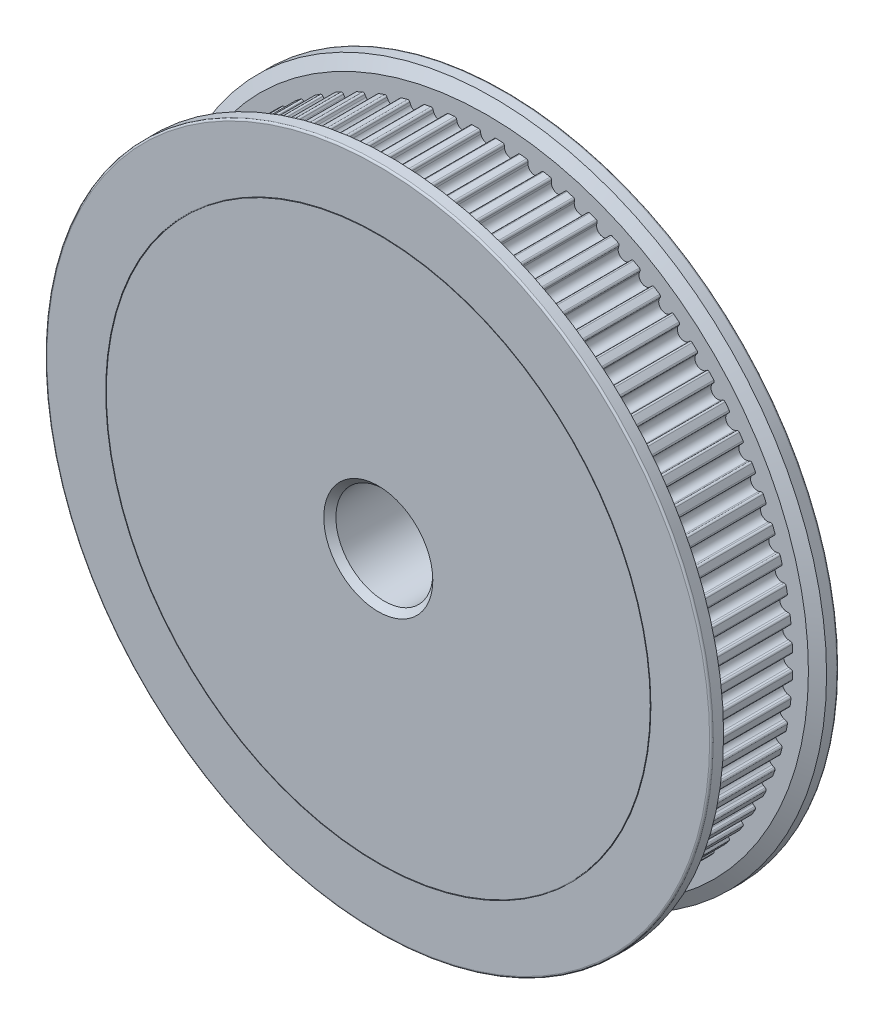
SolidWorks part; units mm, degrees
ref_plane "Front Plane" through (0, 0, 0) normal (0, 0, 1) x (1, 0, 0)
ref_plane "Top Plane" through (0, 0, 0) normal (0, 1, 0) x (1, 0, 0)
ref_plane "Right Plane" through (0, 0, 0) normal (1, 0, 0) x (0, 0, -1)
sketch "Sketch1" plane through (0, 0, 0) normal (0, 0, 1) x (1, 0, 0)
  circle A0 centre (0, 0) radius 15
  dimension "D1" = 30
extrude "Boss-Extrude1" add sketch "Sketch1" along normal blind 6.7
sketch "Sketch2" plane through (0, 0, 6.7) normal (0, 0, 1) x (1, 0, 0)
  circle A0 centre (0, 0) radius 27.5
  dimension "D1" = 55
extrude "Boss-Extrude2" add sketch "Sketch2" along normal blind 1.5 contours A0
sketch "Sketch3" plane through (0, 0, 8.2) normal (0, 0, 1) x (1, 0, 0)
  circle A0 centre (0, 0) radius 25.2
  dimension "D1" = 50.4
extrude "Boss-Extrude3" add sketch "Sketch3" along normal blind 7.5
sketch "Sketch4" plane through (0, 0, 15.7) normal (0, 0, 1) x (1, 0, 0)
  circle A0 centre (0, 0) radius 27.5
extrude "Boss-Extrude4" add sketch "Sketch4" along normal blind 1.5
sketch "Sketch5" plane through (0, 0, 8.2) normal (0, 0, 1) x (1, 0, 0)
  line L0 (0, 0) -> (38.9808, 0) construction
  line L1 (25.1897, 0.7199) -> (25.7855, 0.7199)
  line L2 (25.7855, 0.7199) -> (25.7855, -0.7199)
  line L3 (25.7855, -0.7199) -> (25.1897, -0.7199)
  line L4 (25.1685, -1.2587) -> (25.7625, -1.3054)
  line L5 (25.7625, -1.3054) -> (25.6496, -2.7408)
  line L6 (25.6496, -2.7408) -> (25.0556, -2.694)
  line L7 (24.9922, -3.2295) -> (25.5807, -3.3227)
  line L8 (25.5807, -3.3227) -> (25.3555, -4.7448)
  line L9 (25.3555, -4.7448) -> (24.767, -4.6516)
  line L10 (24.6618, -5.1804) -> (25.2411, -5.3195)
  line L11 (25.2411, -5.3195) -> (24.905, -6.7195)
  line L12 (24.905, -6.7195) -> (24.3257, -6.5804)
  line L13 (24.1793, -7.0994) -> (24.746, -7.2835)
  line L14 (24.746, -7.2835) -> (24.301, -8.6528)
  line L15 (24.301, -8.6528) -> (23.7344, -8.4687)
  line L16 (23.5477, -8.9746) -> (24.0982, -9.2026)
  line L17 (24.0982, -9.2026) -> (23.5472, -10.5328)
  line L18 (23.5472, -10.5328) -> (22.9968, -10.3048)
  line L19 (22.771, -10.7945) -> (23.3019, -11.065)
  line L20 (23.3019, -11.065) -> (22.6483, -12.3478)
  line L21 (22.6483, -12.3478) -> (22.1174, -12.0773)
  line L22 (21.8539, -12.5478) -> (22.3619, -12.8591)
  line L23 (22.3619, -12.8591) -> (21.6096, -14.0867)
  line L24 (21.6096, -14.0867) -> (21.1016, -13.7754)
  line L25 (20.802, -14.2237) -> (21.2841, -14.574)
  line L26 (21.2841, -14.574) -> (20.4378, -15.7388)
  line L27 (20.4378, -15.7388) -> (19.9558, -15.3885)
  line L28 (19.6219, -15.812) -> (20.075, -16.199)
  line L29 (20.075, -16.199) -> (19.1399, -17.2938)
  line L30 (19.1399, -17.2938) -> (18.6869, -16.9068)
  line L31 (18.3209, -17.3028) -> (18.7422, -17.7241)
  line L32 (18.7422, -17.7241) -> (17.7241, -18.7422)
  line L33 (17.7241, -18.7422) -> (17.3028, -18.3209)
  line L34 (16.9068, -18.6869) -> (17.2938, -19.1399)
  line L35 (17.2938, -19.1399) -> (16.199, -20.075)
  line L36 (16.199, -20.075) -> (15.812, -19.6219)
  line L37 (15.3885, -19.9558) -> (15.7388, -20.4378)
  line L38 (15.7388, -20.4378) -> (14.574, -21.2841)
  line L39 (14.574, -21.2841) -> (14.2237, -20.802)
  line L40 (13.7754, -21.1016) -> (14.0867, -21.6096)
  line L41 (14.0867, -21.6096) -> (12.8591, -22.3619)
  line L42 (12.8591, -22.3619) -> (12.5478, -21.8539)
  line L43 (12.0773, -22.1174) -> (12.3478, -22.6483)
  line L44 (12.3478, -22.6483) -> (11.065, -23.3019)
  line L45 (11.065, -23.3019) -> (10.7945, -22.771)
  line L46 (10.3048, -22.9968) -> (10.5328, -23.5472)
  line L47 (10.5328, -23.5472) -> (9.2026, -24.0982)
  line L48 (9.2026, -24.0982) -> (8.9746, -23.5477)
  line L49 (8.4687, -23.7344) -> (8.6528, -24.301)
  line L50 (8.6528, -24.301) -> (7.2835, -24.746)
  line L51 (7.2835, -24.746) -> (7.0994, -24.1793)
  line L52 (6.5804, -24.3257) -> (6.7195, -24.905)
  line L53 (6.7195, -24.905) -> (5.3195, -25.2411)
  line L54 (5.3195, -25.2411) -> (5.1804, -24.6618)
  line L55 (4.6516, -24.767) -> (4.7448, -25.3555)
  line L56 (4.7448, -25.3555) -> (3.3227, -25.5807)
  line L57 (3.3227, -25.5807) -> (3.2295, -24.9922)
  line L58 (2.694, -25.0556) -> (2.7408, -25.6496)
  line L59 (2.7408, -25.6496) -> (1.3054, -25.7625)
  line L60 (1.3054, -25.7625) -> (1.2587, -25.1685)
  line L61 (0.7199, -25.1897) -> (0.7199, -25.7855)
  line L62 (0.7199, -25.7855) -> (-0.7199, -25.7855)
  line L63 (-0.7199, -25.7855) -> (-0.7199, -25.1897)
  line L64 (-1.2587, -25.1685) -> (-1.3054, -25.7625)
  line L65 (-1.3054, -25.7625) -> (-2.7408, -25.6496)
  line L66 (-2.7408, -25.6496) -> (-2.694, -25.0556)
  line L67 (-3.2295, -24.9922) -> (-3.3227, -25.5807)
  line L68 (-3.3227, -25.5807) -> (-4.7448, -25.3555)
  line L69 (-4.7448, -25.3555) -> (-4.6516, -24.767)
  line L70 (-5.1804, -24.6618) -> (-5.3195, -25.2411)
  line L71 (-5.3195, -25.2411) -> (-6.7195, -24.905)
  line L72 (-6.7195, -24.905) -> (-6.5804, -24.3257)
  line L73 (-7.0994, -24.1793) -> (-7.2835, -24.746)
  line L74 (-7.2835, -24.746) -> (-8.6528, -24.301)
  line L75 (-8.6528, -24.301) -> (-8.4687, -23.7344)
  line L76 (-8.9746, -23.5477) -> (-9.2026, -24.0982)
  line L77 (-9.2026, -24.0982) -> (-10.5328, -23.5472)
  line L78 (-10.5328, -23.5472) -> (-10.3048, -22.9968)
  line L79 (-10.7945, -22.771) -> (-11.065, -23.3019)
  line L80 (-11.065, -23.3019) -> (-12.3478, -22.6483)
  line L81 (-12.3478, -22.6483) -> (-12.0773, -22.1174)
  line L82 (-12.5478, -21.8539) -> (-12.8591, -22.3619)
  line L83 (-12.8591, -22.3619) -> (-14.0867, -21.6096)
  line L84 (-14.0867, -21.6096) -> (-13.7754, -21.1016)
  line L85 (-14.2237, -20.802) -> (-14.574, -21.2841)
  line L86 (-14.574, -21.2841) -> (-15.7388, -20.4378)
  line L87 (-15.7388, -20.4378) -> (-15.3885, -19.9558)
  line L88 (-15.812, -19.6219) -> (-16.199, -20.075)
  line L89 (-16.199, -20.075) -> (-17.2938, -19.1399)
  line L90 (-17.2938, -19.1399) -> (-16.9068, -18.6869)
  line L91 (-17.3028, -18.3209) -> (-17.7241, -18.7422)
  line L92 (-17.7241, -18.7422) -> (-18.7422, -17.7241)
  line L93 (-18.7422, -17.7241) -> (-18.3209, -17.3028)
  line L94 (-18.6869, -16.9068) -> (-19.1399, -17.2938)
  line L95 (-19.1399, -17.2938) -> (-20.075, -16.199)
  line L96 (-20.075, -16.199) -> (-19.6219, -15.812)
  line L97 (-19.9558, -15.3885) -> (-20.4378, -15.7388)
  line L98 (-20.4378, -15.7388) -> (-21.2841, -14.574)
  line L99 (-21.2841, -14.574) -> (-20.802, -14.2237)
  line L100 (-21.1016, -13.7754) -> (-21.6096, -14.0867)
  line L101 (-21.6096, -14.0867) -> (-22.3619, -12.8591)
  line L102 (-22.3619, -12.8591) -> (-21.8539, -12.5478)
  line L103 (-22.1174, -12.0773) -> (-22.6483, -12.3478)
  line L104 (-22.6483, -12.3478) -> (-23.3019, -11.065)
  line L105 (-23.3019, -11.065) -> (-22.771, -10.7945)
  line L106 (-22.9968, -10.3048) -> (-23.5472, -10.5328)
  line L107 (-23.5472, -10.5328) -> (-24.0982, -9.2026)
  line L108 (-24.0982, -9.2026) -> (-23.5477, -8.9746)
  line L109 (-23.7344, -8.4687) -> (-24.301, -8.6528)
  line L110 (-24.301, -8.6528) -> (-24.746, -7.2835)
  line L111 (-24.746, -7.2835) -> (-24.1793, -7.0994)
  line L112 (-24.3257, -6.5804) -> (-24.905, -6.7195)
  line L113 (-24.905, -6.7195) -> (-25.2411, -5.3195)
  line L114 (-25.2411, -5.3195) -> (-24.6618, -5.1804)
  line L115 (-24.767, -4.6516) -> (-25.3555, -4.7448)
  line L116 (-25.3555, -4.7448) -> (-25.5807, -3.3227)
  line L117 (-25.5807, -3.3227) -> (-24.9922, -3.2295)
  line L118 (-25.0556, -2.694) -> (-25.6496, -2.7408)
  line L119 (-25.6496, -2.7408) -> (-25.7625, -1.3054)
  line L120 (-25.7625, -1.3054) -> (-25.1685, -1.2587)
  line L121 (-25.1897, -0.7199) -> (-25.7855, -0.7199)
  line L122 (-25.7855, -0.7199) -> (-25.7855, 0.7199)
  line L123 (-25.7855, 0.7199) -> (-25.1897, 0.7199)
  line L124 (-25.1685, 1.2587) -> (-25.7625, 1.3054)
  line L125 (-25.7625, 1.3054) -> (-25.6496, 2.7408)
  line L126 (-25.6496, 2.7408) -> (-25.0556, 2.694)
  line L127 (-24.9922, 3.2295) -> (-25.5807, 3.3227)
  line L128 (-25.5807, 3.3227) -> (-25.3555, 4.7448)
  line L129 (-25.3555, 4.7448) -> (-24.767, 4.6516)
  line L130 (-24.6618, 5.1804) -> (-25.2411, 5.3195)
  line L131 (-25.2411, 5.3195) -> (-24.905, 6.7195)
  line L132 (-24.905, 6.7195) -> (-24.3257, 6.5804)
  line L133 (-24.1793, 7.0994) -> (-24.746, 7.2835)
  line L134 (-24.746, 7.2835) -> (-24.301, 8.6528)
  line L135 (-24.301, 8.6528) -> (-23.7344, 8.4687)
  line L136 (-23.5477, 8.9746) -> (-24.0982, 9.2026)
  line L137 (-24.0982, 9.2026) -> (-23.5472, 10.5328)
  line L138 (-23.5472, 10.5328) -> (-22.9968, 10.3048)
  line L139 (-22.771, 10.7945) -> (-23.3019, 11.065)
  line L140 (-23.3019, 11.065) -> (-22.6483, 12.3478)
  line L141 (-22.6483, 12.3478) -> (-22.1174, 12.0773)
  line L142 (-21.8539, 12.5478) -> (-22.3619, 12.8591)
  line L143 (-22.3619, 12.8591) -> (-21.6096, 14.0867)
  line L144 (-21.6096, 14.0867) -> (-21.1016, 13.7754)
  line L145 (-20.802, 14.2237) -> (-21.2841, 14.574)
  line L146 (-21.2841, 14.574) -> (-20.4378, 15.7388)
  line L147 (-20.4378, 15.7388) -> (-19.9558, 15.3885)
  line L148 (-19.6219, 15.812) -> (-20.075, 16.199)
  line L149 (-20.075, 16.199) -> (-19.1399, 17.2938)
  line L150 (-19.1399, 17.2938) -> (-18.6869, 16.9068)
  line L151 (-18.3209, 17.3028) -> (-18.7422, 17.7241)
  line L152 (-18.7422, 17.7241) -> (-17.7241, 18.7422)
  line L153 (-17.7241, 18.7422) -> (-17.3028, 18.3209)
  line L154 (-16.9068, 18.6869) -> (-17.2938, 19.1399)
  line L155 (-17.2938, 19.1399) -> (-16.199, 20.075)
  line L156 (-16.199, 20.075) -> (-15.812, 19.6219)
  line L157 (-15.3885, 19.9558) -> (-15.7388, 20.4378)
  line L158 (-15.7388, 20.4378) -> (-14.574, 21.2841)
  line L159 (-14.574, 21.2841) -> (-14.2237, 20.802)
  line L160 (-13.7754, 21.1016) -> (-14.0867, 21.6096)
  line L161 (-14.0867, 21.6096) -> (-12.8591, 22.3619)
  line L162 (-12.8591, 22.3619) -> (-12.5478, 21.8539)
  line L163 (-12.0773, 22.1174) -> (-12.3478, 22.6483)
  line L164 (-12.3478, 22.6483) -> (-11.065, 23.3019)
  line L165 (-11.065, 23.3019) -> (-10.7945, 22.771)
  line L166 (-10.3048, 22.9968) -> (-10.5328, 23.5472)
  line L167 (-10.5328, 23.5472) -> (-9.2026, 24.0982)
  line L168 (-9.2026, 24.0982) -> (-8.9746, 23.5477)
  line L169 (-8.4687, 23.7344) -> (-8.6528, 24.301)
  line L170 (-8.6528, 24.301) -> (-7.2835, 24.746)
  line L171 (-7.2835, 24.746) -> (-7.0994, 24.1793)
  line L172 (-6.5804, 24.3257) -> (-6.7195, 24.905)
  line L173 (-6.7195, 24.905) -> (-5.3195, 25.2411)
  line L174 (-5.3195, 25.2411) -> (-5.1804, 24.6618)
  line L175 (-4.6516, 24.767) -> (-4.7448, 25.3555)
  line L176 (-4.7448, 25.3555) -> (-3.3227, 25.5807)
  line L177 (-3.3227, 25.5807) -> (-3.2295, 24.9922)
  line L178 (-2.694, 25.0556) -> (-2.7408, 25.6496)
  line L179 (-2.7408, 25.6496) -> (-1.3054, 25.7625)
  line L180 (-1.3054, 25.7625) -> (-1.2587, 25.1685)
  line L181 (-0.7199, 25.1897) -> (-0.7199, 25.7855)
  line L182 (-0.7199, 25.7855) -> (0.7199, 25.7855)
  line L183 (0.7199, 25.7855) -> (0.7199, 25.1897)
  line L184 (1.2587, 25.1685) -> (1.3054, 25.7625)
  line L185 (1.3054, 25.7625) -> (2.7408, 25.6496)
  line L186 (2.7408, 25.6496) -> (2.694, 25.0556)
  line L187 (3.2295, 24.9922) -> (3.3227, 25.5807)
  line L188 (3.3227, 25.5807) -> (4.7448, 25.3555)
  line L189 (4.7448, 25.3555) -> (4.6516, 24.767)
  line L190 (5.1804, 24.6618) -> (5.3195, 25.2411)
  line L191 (5.3195, 25.2411) -> (6.7195, 24.905)
  line L192 (6.7195, 24.905) -> (6.5804, 24.3257)
  line L193 (7.0994, 24.1793) -> (7.2835, 24.746)
  line L194 (7.2835, 24.746) -> (8.6528, 24.301)
  line L195 (8.6528, 24.301) -> (8.4687, 23.7344)
  line L196 (8.9746, 23.5477) -> (9.2026, 24.0982)
  line L197 (9.2026, 24.0982) -> (10.5328, 23.5472)
  line L198 (10.5328, 23.5472) -> (10.3048, 22.9968)
  line L199 (10.7945, 22.771) -> (11.065, 23.3019)
  line L200 (11.065, 23.3019) -> (12.3478, 22.6483)
  line L201 (12.3478, 22.6483) -> (12.0773, 22.1174)
  line L202 (12.5478, 21.8539) -> (12.8591, 22.3619)
  line L203 (12.8591, 22.3619) -> (14.0867, 21.6096)
  line L204 (14.0867, 21.6096) -> (13.7754, 21.1016)
  line L205 (14.2237, 20.802) -> (14.574, 21.2841)
  line L206 (14.574, 21.2841) -> (15.7388, 20.4378)
  line L207 (15.7388, 20.4378) -> (15.3885, 19.9558)
  line L208 (15.812, 19.6219) -> (16.199, 20.075)
  line L209 (16.199, 20.075) -> (17.2938, 19.1399)
  line L210 (17.2938, 19.1399) -> (16.9068, 18.6869)
  line L211 (17.3028, 18.3209) -> (17.7241, 18.7422)
  line L212 (17.7241, 18.7422) -> (18.7422, 17.7241)
  line L213 (18.7422, 17.7241) -> (18.3209, 17.3028)
  line L214 (18.6869, 16.9068) -> (19.1399, 17.2938)
  line L215 (19.1399, 17.2938) -> (20.075, 16.199)
  line L216 (20.075, 16.199) -> (19.6219, 15.812)
  line L217 (19.9558, 15.3885) -> (20.4378, 15.7388)
  line L218 (20.4378, 15.7388) -> (21.2841, 14.574)
  line L219 (21.2841, 14.574) -> (20.802, 14.2237)
  line L220 (21.1016, 13.7754) -> (21.6096, 14.0867)
  line L221 (21.6096, 14.0867) -> (22.3619, 12.8591)
  line L222 (22.3619, 12.8591) -> (21.8539, 12.5478)
  line L223 (22.1174, 12.0773) -> (22.6483, 12.3478)
  line L224 (22.6483, 12.3478) -> (23.3019, 11.065)
  line L225 (23.3019, 11.065) -> (22.771, 10.7945)
  line L226 (22.9968, 10.3048) -> (23.5472, 10.5328)
  line L227 (23.5472, 10.5328) -> (24.0982, 9.2026)
  line L228 (24.0982, 9.2026) -> (23.5477, 8.9746)
  line L229 (23.7344, 8.4687) -> (24.301, 8.6528)
  line L230 (24.301, 8.6528) -> (24.746, 7.2835)
  line L231 (24.746, 7.2835) -> (24.1793, 7.0994)
  line L232 (24.3257, 6.5804) -> (24.905, 6.7195)
  line L233 (24.905, 6.7195) -> (25.2411, 5.3195)
  line L234 (25.2411, 5.3195) -> (24.6618, 5.1804)
  line L235 (24.767, 4.6516) -> (25.3555, 4.7448)
  line L236 (25.3555, 4.7448) -> (25.5807, 3.3227)
  line L237 (25.5807, 3.3227) -> (24.9922, 3.2295)
  line L238 (25.0556, 2.694) -> (25.6496, 2.7408)
  line L239 (25.6496, 2.7408) -> (25.7625, 1.3054)
  line L240 (25.7625, 1.3054) -> (25.1685, 1.2587)
  circle A0 centre (0, 0) radius 25.45 construction
  circle A1 centre (0, 0) radius 25.2 construction
  arc A2 (24.8691, 0.5381) -> (24.8691, -0.5381) centre (25.005, 0) ccw
  arc A4 (24.8346, -1.4148) -> (24.7502, -2.4876) centre (24.9279, -1.9619) ccw
  arc A5 (25.0159, -1.4012) -> (25.1685, -1.2587) centre (25.0187, -1.2512) ccw
  arc A6 (25.0487, 0.5659) -> (25.1897, 0.7199) centre (25.0398, 0.7156) ccw
  arc A7 (25.0487, -0.5659) -> (25.1897, -0.7199) centre (25.0398, -0.7156) cw
  arc A8 (25.0487, 0.5659) -> (24.8691, 0.5381) centre (25.106, -0.4) ccw
  arc A9 (25.0487, -0.5659) -> (24.8691, -0.5381) centre (25.106, 0.4) cw
  arc A10 (24.9271, -2.5294) -> (25.0556, -2.694) centre (24.9064, -2.678) cw
  arc A11 (25.0159, -1.4012) -> (24.8346, -1.4148) centre (24.9973, -2.3686) ccw
  arc A12 (24.9271, -2.5294) -> (24.7502, -2.4876) centre (25.06, -1.571) cw
  circle A13 centre (0, 0) radius 25.45 construction
  circle A14 centre (0, 0) radius 25.2 construction
  arc A15 (24.6471, -3.3589) -> (24.4787, -4.4219) centre (24.6971, -3.9116) ccw
  arc A16 (24.8288, -3.3596) -> (24.9922, -3.2295) centre (24.8434, -3.2103) ccw
  arc A17 (24.6518, -4.4774) -> (24.767, -4.6516) centre (24.6196, -4.6239) cw
  arc A18 (24.8288, -3.3596) -> (24.6471, -3.3589) centre (24.7344, -4.3225) ccw
  arc A19 (24.6518, -4.4774) -> (24.4787, -4.4219) centre (24.8595, -3.5324) cw
  circle A20 centre (0, 0) radius 25.45 construction
  circle A21 centre (0, 0) radius 25.2 construction
  arc A22 (24.3076, -5.2823) -> (24.0563, -6.3288) centre (24.3141, -5.8373) ccw
  arc A23 (24.4887, -5.2973) -> (24.6618, -5.1804) centre (24.515, -5.1496) ccw
  arc A24 (24.2245, -6.3977) -> (24.3257, -6.5804) centre (24.1809, -6.5412) cw
  arc A25 (24.4887, -5.2973) -> (24.3076, -5.2823) centre (24.319, -6.2498) ccw
  arc A26 (24.2245, -6.3977) -> (24.0563, -6.3288) centre (24.5057, -5.4719) cw
  circle A27 centre (0, 0) radius 25.45 construction
  circle A28 centre (0, 0) radius 25.2 construction
  arc A29 (23.8182, -7.1732) -> (23.4856, -8.1967) centre (23.7812, -7.727) ccw
  arc A30 (23.9976, -7.2023) -> (24.1793, -7.0994) centre (24.0354, -7.0571) ccw
  arc A31 (23.6478, -8.2786) -> (23.7344, -8.4687) centre (23.5931, -8.4183) cw
  arc A32 (23.9976, -7.2023) -> (23.8182, -7.1732) centre (23.7537, -8.1386) ccw
  arc A33 (23.6478, -8.2786) -> (23.4856, -8.1967) centre (24.0009, -7.3778) cw
  circle A34 centre (0, 0) radius 25.45 construction
  circle A35 centre (0, 0) radius 25.2 construction
  arc A36 (23.182, -9.0198) -> (22.7701, -10.0141) centre (23.1016, -9.569) ccw
  arc A37 (23.3585, -9.0629) -> (23.5477, -8.9746) centre (23.4076, -8.9212) ccw
  arc A38 (22.9254, -10.1085) -> (22.9968, -10.3048) centre (22.8599, -10.2434) cw
  arc A39 (23.3585, -9.0629) -> (23.182, -9.0198) centre (23.0419, -9.9772) ccw
  arc A40 (22.9254, -10.1085) -> (22.7701, -10.0141) centre (23.348, -9.2381) cw
  circle A41 centre (0, 0) radius 25.45 construction
  circle A42 centre (0, 0) radius 25.2 construction
  arc A43 (22.4028, -10.8109) -> (21.9142, -11.7698) centre (22.2796, -11.352) ccw
  arc A44 (22.5754, -10.8677) -> (22.771, -10.7945) centre (22.6355, -10.7302) ccw
  arc A45 (22.0616, -11.876) -> (22.1174, -12.0773) centre (21.9857, -12.0054) cw
  arc A46 (22.5754, -10.8677) -> (22.4028, -10.8109) centre (22.188, -11.7543) ccw
  arc A47 (22.0616, -11.876) -> (21.9142, -11.7698) centre (22.5512, -11.0415) cw
  circle A48 centre (0, 0) radius 25.45 construction
  circle A49 centre (0, 0) radius 25.2 construction
  arc A50 (21.4855, -12.5353) -> (20.9232, -13.4529) centre (21.3203, -13.0651) ccw
  arc A51 (21.6532, -12.6054) -> (21.8539, -12.5478) centre (21.7238, -12.4731) ccw
  arc A52 (21.0618, -13.5704) -> (21.1016, -13.7754) centre (20.976, -13.6934) cw
  arc A53 (21.6532, -12.6054) -> (21.4855, -12.5353) centre (21.1974, -13.4589) ccw
  arc A54 (21.0618, -13.5704) -> (20.9232, -13.4529) centre (21.6154, -12.7768) cw
  circle A55 centre (0, 0) radius 25.45 construction
  circle A56 centre (0, 0) radius 25.2 construction
  arc A57 (20.4358, -14.1823) -> (19.8032, -15.053) centre (20.2295, -14.6976) ccw
  arc A58 (20.5974, -14.2654) -> (20.802, -14.2237) centre (20.6782, -14.1391) ccw
  arc A59 (19.9322, -15.181) -> (19.9558, -15.3885) centre (19.837, -15.2969) cw
  arc A60 (20.5974, -14.2654) -> (20.4358, -14.1823) centre (20.0761, -15.0806) ccw
  arc A61 (19.9322, -15.181) -> (19.8032, -15.053) centre (20.5463, -14.4334) cw
  circle A62 centre (0, 0) radius 25.45 construction
  circle A63 centre (0, 0) radius 25.2 construction
  arc A64 (19.2601, -15.742) -> (18.5611, -16.5603) centre (19.014, -16.2394) ccw
  arc A65 (19.4147, -15.8375) -> (19.6219, -15.812) centre (19.5051, -15.7179) ccw
  arc A66 (18.6797, -16.6981) -> (18.6869, -16.9068) centre (18.5757, -16.8062) cw
  arc A67 (19.4147, -15.8375) -> (19.2601, -15.742) centre (18.831, -16.6092) ccw
  arc A68 (18.6797, -16.6981) -> (18.5611, -16.5603) centre (19.3506, -16.0009) cw
  circle A69 centre (0, 0) radius 25.45 construction
  circle A70 centre (0, 0) radius 25.2 construction
  arc A71 (17.9656, -17.2046) -> (17.2046, -17.9656) centre (17.6812, -17.6812) ccw
  arc A72 (18.1122, -17.312) -> (18.3209, -17.3028) centre (18.2118, -17.1998) ccw
  arc A73 (17.312, -18.1122) -> (17.3028, -18.3209) centre (17.1998, -18.2118) cw
  arc A74 (18.1122, -17.312) -> (17.9656, -17.2046) centre (17.4698, -18.0355) ccw
  arc A75 (17.312, -18.1122) -> (17.2046, -17.9656) centre (18.0355, -17.4698) cw
  circle A76 centre (0, 0) radius 25.45 construction
  circle A77 centre (0, 0) radius 25.2 construction
  arc A78 (16.5603, -18.5611) -> (15.742, -19.2601) centre (16.2394, -19.014) ccw
  arc A79 (16.6981, -18.6797) -> (16.9068, -18.6869) centre (16.8062, -18.5757) ccw
  arc A80 (15.8375, -19.4147) -> (15.812, -19.6219) centre (15.7179, -19.5051) cw
  arc A81 (16.6981, -18.6797) -> (16.5603, -18.5611) centre (16.0009, -19.3506) ccw
  arc A82 (15.8375, -19.4147) -> (15.742, -19.2601) centre (16.6092, -18.831) cw
  circle A83 centre (0, 0) radius 25.45 construction
  circle A84 centre (0, 0) radius 25.2 construction
  arc A85 (15.053, -19.8032) -> (14.1823, -20.4358) centre (14.6976, -20.2295) ccw
  arc A86 (15.181, -19.9322) -> (15.3885, -19.9558) centre (15.2969, -19.837) ccw
  arc A87 (14.2654, -20.5974) -> (14.2237, -20.802) centre (14.1391, -20.6782) cw
  arc A88 (15.181, -19.9322) -> (15.053, -19.8032) centre (14.4334, -20.5463) ccw
  arc A89 (14.2654, -20.5974) -> (14.1823, -20.4358) centre (15.0806, -20.0761) cw
  circle A90 centre (0, 0) radius 25.45 construction
  circle A91 centre (0, 0) radius 25.2 construction
  arc A92 (13.4529, -20.9232) -> (12.5353, -21.4855) centre (13.0651, -21.3203) ccw
  arc A93 (13.5704, -21.0618) -> (13.7754, -21.1016) centre (13.6934, -20.976) ccw
  arc A94 (12.6054, -21.6532) -> (12.5478, -21.8539) centre (12.4731, -21.7238) cw
  arc A95 (13.5704, -21.0618) -> (13.4529, -20.9232) centre (12.7768, -21.6154) ccw
  arc A96 (12.6054, -21.6532) -> (12.5353, -21.4855) centre (13.4589, -21.1974) cw
  circle A97 centre (0, 0) radius 25.45 construction
  circle A98 centre (0, 0) radius 25.2 construction
  arc A99 (11.7698, -21.9142) -> (10.8109, -22.4028) centre (11.352, -22.2796) ccw
  arc A100 (11.876, -22.0616) -> (12.0773, -22.1174) centre (12.0054, -21.9857) ccw
  arc A101 (10.8677, -22.5754) -> (10.7945, -22.771) centre (10.7302, -22.6355) cw
  arc A102 (11.876, -22.0616) -> (11.7698, -21.9142) centre (11.0415, -22.5512) ccw
  arc A103 (10.8677, -22.5754) -> (10.8109, -22.4028) centre (11.7543, -22.188) cw
  circle A104 centre (0, 0) radius 25.45 construction
  circle A105 centre (0, 0) radius 25.2 construction
  arc A106 (10.0141, -22.7701) -> (9.0198, -23.182) centre (9.569, -23.1016) ccw
  arc A107 (10.1085, -22.9254) -> (10.3048, -22.9968) centre (10.2434, -22.8599) ccw
  arc A108 (9.0629, -23.3585) -> (8.9746, -23.5477) centre (8.9212, -23.4076) cw
  arc A109 (10.1085, -22.9254) -> (10.0141, -22.7701) centre (9.2381, -23.348) ccw
  arc A110 (9.0629, -23.3585) -> (9.0198, -23.182) centre (9.9772, -23.0419) cw
  circle A111 centre (0, 0) radius 25.45 construction
  circle A112 centre (0, 0) radius 25.2 construction
  arc A113 (8.1967, -23.4856) -> (7.1732, -23.8182) centre (7.727, -23.7812) ccw
  arc A114 (8.2786, -23.6478) -> (8.4687, -23.7344) centre (8.4183, -23.5931) ccw
  arc A115 (7.2023, -23.9976) -> (7.0994, -24.1793) centre (7.0571, -24.0354) cw
  arc A116 (8.2786, -23.6478) -> (8.1967, -23.4856) centre (7.3778, -24.0009) ccw
  arc A117 (7.2023, -23.9976) -> (7.1732, -23.8182) centre (8.1386, -23.7537) cw
  circle A118 centre (0, 0) radius 25.45 construction
  circle A119 centre (0, 0) radius 25.2 construction
  arc A120 (6.3288, -24.0563) -> (5.2823, -24.3076) centre (5.8373, -24.3141) ccw
  arc A121 (6.3977, -24.2245) -> (6.5804, -24.3257) centre (6.5412, -24.1809) ccw
  arc A122 (5.2973, -24.4887) -> (5.1804, -24.6618) centre (5.1496, -24.515) cw
  arc A123 (6.3977, -24.2245) -> (6.3288, -24.0563) centre (5.4719, -24.5057) ccw
  arc A124 (5.2973, -24.4887) -> (5.2823, -24.3076) centre (6.2498, -24.319) cw
  circle A125 centre (0, 0) radius 25.45 construction
  circle A126 centre (0, 0) radius 25.2 construction
  arc A127 (4.4219, -24.4787) -> (3.3589, -24.6471) centre (3.9116, -24.6971) ccw
  arc A128 (4.4774, -24.6518) -> (4.6516, -24.767) centre (4.6239, -24.6196) ccw
  arc A129 (3.3596, -24.8288) -> (3.2295, -24.9922) centre (3.2103, -24.8434) cw
  arc A130 (4.4774, -24.6518) -> (4.4219, -24.4787) centre (3.5324, -24.8595) ccw
  arc A131 (3.3596, -24.8288) -> (3.3589, -24.6471) centre (4.3225, -24.7344) cw
  circle A132 centre (0, 0) radius 25.45 construction
  circle A133 centre (0, 0) radius 25.2 construction
  arc A134 (2.4876, -24.7502) -> (1.4148, -24.8346) centre (1.9619, -24.9279) ccw
  arc A135 (2.5294, -24.9271) -> (2.694, -25.0556) centre (2.678, -24.9064) ccw
  arc A136 (1.4012, -25.0159) -> (1.2587, -25.1685) centre (1.2512, -25.0187) cw
  arc A137 (2.5294, -24.9271) -> (2.4876, -24.7502) centre (1.571, -25.06) ccw
  arc A138 (1.4012, -25.0159) -> (1.4148, -24.8346) centre (2.3686, -24.9973) cw
  circle A139 centre (0, 0) radius 25.45 construction
  circle A140 centre (0, 0) radius 25.2 construction
  arc A141 (0.5381, -24.8691) -> (-0.5381, -24.8691) centre (0, -25.005) ccw
  arc A142 (0.5659, -25.0487) -> (0.7199, -25.1897) centre (0.7156, -25.0398) ccw
  arc A143 (-0.5659, -25.0487) -> (-0.7199, -25.1897) centre (-0.7156, -25.0398) cw
  arc A144 (0.5659, -25.0487) -> (0.5381, -24.8691) centre (-0.4, -25.106) ccw
  arc A145 (-0.5659, -25.0487) -> (-0.5381, -24.8691) centre (0.4, -25.106) cw
  circle A146 centre (0, 0) radius 25.45 construction
  circle A147 centre (0, 0) radius 25.2 construction
  arc A148 (-1.4148, -24.8346) -> (-2.4876, -24.7502) centre (-1.9619, -24.9279) ccw
  arc A149 (-1.4012, -25.0159) -> (-1.2587, -25.1685) centre (-1.2512, -25.0187) ccw
  arc A150 (-2.5294, -24.9271) -> (-2.694, -25.0556) centre (-2.678, -24.9064) cw
  arc A151 (-1.4012, -25.0159) -> (-1.4148, -24.8346) centre (-2.3686, -24.9973) ccw
  arc A152 (-2.5294, -24.9271) -> (-2.4876, -24.7502) centre (-1.571, -25.06) cw
  circle A153 centre (0, 0) radius 25.45 construction
  circle A154 centre (0, 0) radius 25.2 construction
  arc A155 (-3.3589, -24.6471) -> (-4.4219, -24.4787) centre (-3.9116, -24.6971) ccw
  arc A156 (-3.3596, -24.8288) -> (-3.2295, -24.9922) centre (-3.2103, -24.8434) ccw
  arc A157 (-4.4774, -24.6518) -> (-4.6516, -24.767) centre (-4.6239, -24.6196) cw
  arc A158 (-3.3596, -24.8288) -> (-3.3589, -24.6471) centre (-4.3225, -24.7344) ccw
  arc A159 (-4.4774, -24.6518) -> (-4.4219, -24.4787) centre (-3.5324, -24.8595) cw
  circle A160 centre (0, 0) radius 25.45 construction
  circle A161 centre (0, 0) radius 25.2 construction
  arc A162 (-5.2823, -24.3076) -> (-6.3288, -24.0563) centre (-5.8373, -24.3141) ccw
  arc A163 (-5.2973, -24.4887) -> (-5.1804, -24.6618) centre (-5.1496, -24.515) ccw
  arc A164 (-6.3977, -24.2245) -> (-6.5804, -24.3257) centre (-6.5412, -24.1809) cw
  arc A165 (-5.2973, -24.4887) -> (-5.2823, -24.3076) centre (-6.2498, -24.319) ccw
  arc A166 (-6.3977, -24.2245) -> (-6.3288, -24.0563) centre (-5.4719, -24.5057) cw
  circle A167 centre (0, 0) radius 25.45 construction
  circle A168 centre (0, 0) radius 25.2 construction
  arc A169 (-7.1732, -23.8182) -> (-8.1967, -23.4856) centre (-7.727, -23.7812) ccw
  arc A170 (-7.2023, -23.9976) -> (-7.0994, -24.1793) centre (-7.0571, -24.0354) ccw
  arc A171 (-8.2786, -23.6478) -> (-8.4687, -23.7344) centre (-8.4183, -23.5931) cw
  arc A172 (-7.2023, -23.9976) -> (-7.1732, -23.8182) centre (-8.1386, -23.7537) ccw
  arc A173 (-8.2786, -23.6478) -> (-8.1967, -23.4856) centre (-7.3778, -24.0009) cw
  circle A174 centre (0, 0) radius 25.45 construction
  circle A175 centre (0, 0) radius 25.2 construction
  arc A176 (-9.0198, -23.182) -> (-10.0141, -22.7701) centre (-9.569, -23.1016) ccw
  arc A177 (-9.0629, -23.3585) -> (-8.9746, -23.5477) centre (-8.9212, -23.4076) ccw
  arc A178 (-10.1085, -22.9254) -> (-10.3048, -22.9968) centre (-10.2434, -22.8599) cw
  arc A179 (-9.0629, -23.3585) -> (-9.0198, -23.182) centre (-9.9772, -23.0419) ccw
  arc A180 (-10.1085, -22.9254) -> (-10.0141, -22.7701) centre (-9.2381, -23.348) cw
  circle A181 centre (0, 0) radius 25.45 construction
  circle A182 centre (0, 0) radius 25.2 construction
  arc A183 (-10.8109, -22.4028) -> (-11.7698, -21.9142) centre (-11.352, -22.2796) ccw
  arc A184 (-10.8677, -22.5754) -> (-10.7945, -22.771) centre (-10.7302, -22.6355) ccw
  arc A185 (-11.876, -22.0616) -> (-12.0773, -22.1174) centre (-12.0054, -21.9857) cw
  arc A186 (-10.8677, -22.5754) -> (-10.8109, -22.4028) centre (-11.7543, -22.188) ccw
  arc A187 (-11.876, -22.0616) -> (-11.7698, -21.9142) centre (-11.0415, -22.5512) cw
  circle A188 centre (0, 0) radius 25.45 construction
  circle A189 centre (0, 0) radius 25.2 construction
  arc A190 (-12.5353, -21.4855) -> (-13.4529, -20.9232) centre (-13.0651, -21.3203) ccw
  arc A191 (-12.6054, -21.6532) -> (-12.5478, -21.8539) centre (-12.4731, -21.7238) ccw
  arc A192 (-13.5704, -21.0618) -> (-13.7754, -21.1016) centre (-13.6934, -20.976) cw
  arc A193 (-12.6054, -21.6532) -> (-12.5353, -21.4855) centre (-13.4589, -21.1974) ccw
  arc A194 (-13.5704, -21.0618) -> (-13.4529, -20.9232) centre (-12.7768, -21.6154) cw
  circle A195 centre (0, 0) radius 25.45 construction
  circle A196 centre (0, 0) radius 25.2 construction
  arc A197 (-14.1823, -20.4358) -> (-15.053, -19.8032) centre (-14.6976, -20.2295) ccw
  arc A198 (-14.2654, -20.5974) -> (-14.2237, -20.802) centre (-14.1391, -20.6782) ccw
  arc A199 (-15.181, -19.9322) -> (-15.3885, -19.9558) centre (-15.2969, -19.837) cw
  arc A200 (-14.2654, -20.5974) -> (-14.1823, -20.4358) centre (-15.0806, -20.0761) ccw
  arc A201 (-15.181, -19.9322) -> (-15.053, -19.8032) centre (-14.4334, -20.5463) cw
  circle A202 centre (0, 0) radius 25.45 construction
  circle A203 centre (0, 0) radius 25.2 construction
  arc A204 (-15.742, -19.2601) -> (-16.5603, -18.5611) centre (-16.2394, -19.014) ccw
  arc A205 (-15.8375, -19.4147) -> (-15.812, -19.6219) centre (-15.7179, -19.5051) ccw
  arc A206 (-16.6981, -18.6797) -> (-16.9068, -18.6869) centre (-16.8062, -18.5757) cw
  arc A207 (-15.8375, -19.4147) -> (-15.742, -19.2601) centre (-16.6092, -18.831) ccw
  arc A208 (-16.6981, -18.6797) -> (-16.5603, -18.5611) centre (-16.0009, -19.3506) cw
  circle A209 centre (0, 0) radius 25.45 construction
  circle A210 centre (0, 0) radius 25.2 construction
  arc A211 (-17.2046, -17.9656) -> (-17.9656, -17.2046) centre (-17.6812, -17.6812) ccw
  arc A212 (-17.312, -18.1122) -> (-17.3028, -18.3209) centre (-17.1998, -18.2118) ccw
  arc A213 (-18.1122, -17.312) -> (-18.3209, -17.3028) centre (-18.2118, -17.1998) cw
  arc A214 (-17.312, -18.1122) -> (-17.2046, -17.9656) centre (-18.0355, -17.4698) ccw
  arc A215 (-18.1122, -17.312) -> (-17.9656, -17.2046) centre (-17.4698, -18.0355) cw
  circle A216 centre (0, 0) radius 25.45 construction
  circle A217 centre (0, 0) radius 25.2 construction
  arc A218 (-18.5611, -16.5603) -> (-19.2601, -15.742) centre (-19.014, -16.2394) ccw
  arc A219 (-18.6797, -16.6981) -> (-18.6869, -16.9068) centre (-18.5757, -16.8062) ccw
  arc A220 (-19.4147, -15.8375) -> (-19.6219, -15.812) centre (-19.5051, -15.7179) cw
  arc A221 (-18.6797, -16.6981) -> (-18.5611, -16.5603) centre (-19.3506, -16.0009) ccw
  arc A222 (-19.4147, -15.8375) -> (-19.2601, -15.742) centre (-18.831, -16.6092) cw
  circle A223 centre (0, 0) radius 25.45 construction
  circle A224 centre (0, 0) radius 25.2 construction
  arc A225 (-19.8032, -15.053) -> (-20.4358, -14.1823) centre (-20.2295, -14.6976) ccw
  arc A226 (-19.9322, -15.181) -> (-19.9558, -15.3885) centre (-19.837, -15.2969) ccw
  arc A227 (-20.5974, -14.2654) -> (-20.802, -14.2237) centre (-20.6782, -14.1391) cw
  arc A228 (-19.9322, -15.181) -> (-19.8032, -15.053) centre (-20.5463, -14.4334) ccw
  arc A229 (-20.5974, -14.2654) -> (-20.4358, -14.1823) centre (-20.0761, -15.0806) cw
  circle A230 centre (0, 0) radius 25.45 construction
  circle A231 centre (0, 0) radius 25.2 construction
  arc A232 (-20.9232, -13.4529) -> (-21.4855, -12.5353) centre (-21.3203, -13.0651) ccw
  arc A233 (-21.0618, -13.5704) -> (-21.1016, -13.7754) centre (-20.976, -13.6934) ccw
  arc A234 (-21.6532, -12.6054) -> (-21.8539, -12.5478) centre (-21.7238, -12.4731) cw
  arc A235 (-21.0618, -13.5704) -> (-20.9232, -13.4529) centre (-21.6154, -12.7768) ccw
  arc A236 (-21.6532, -12.6054) -> (-21.4855, -12.5353) centre (-21.1974, -13.4589) cw
  circle A237 centre (0, 0) radius 25.45 construction
  circle A238 centre (0, 0) radius 25.2 construction
  arc A239 (-21.9142, -11.7698) -> (-22.4028, -10.8109) centre (-22.2796, -11.352) ccw
  arc A240 (-22.0616, -11.876) -> (-22.1174, -12.0773) centre (-21.9857, -12.0054) ccw
  arc A241 (-22.5754, -10.8677) -> (-22.771, -10.7945) centre (-22.6355, -10.7302) cw
  arc A242 (-22.0616, -11.876) -> (-21.9142, -11.7698) centre (-22.5512, -11.0415) ccw
  arc A243 (-22.5754, -10.8677) -> (-22.4028, -10.8109) centre (-22.188, -11.7543) cw
  circle A244 centre (0, 0) radius 25.45 construction
  circle A245 centre (0, 0) radius 25.2 construction
  arc A246 (-22.7701, -10.0141) -> (-23.182, -9.0198) centre (-23.1016, -9.569) ccw
  arc A247 (-22.9254, -10.1085) -> (-22.9968, -10.3048) centre (-22.8599, -10.2434) ccw
  arc A248 (-23.3585, -9.0629) -> (-23.5477, -8.9746) centre (-23.4076, -8.9212) cw
  arc A249 (-22.9254, -10.1085) -> (-22.7701, -10.0141) centre (-23.348, -9.2381) ccw
  arc A250 (-23.3585, -9.0629) -> (-23.182, -9.0198) centre (-23.0419, -9.9772) cw
  circle A251 centre (0, 0) radius 25.45 construction
  circle A252 centre (0, 0) radius 25.2 construction
  arc A253 (-23.4856, -8.1967) -> (-23.8182, -7.1732) centre (-23.7812, -7.727) ccw
  arc A254 (-23.6478, -8.2786) -> (-23.7344, -8.4687) centre (-23.5931, -8.4183) ccw
  arc A255 (-23.9976, -7.2023) -> (-24.1793, -7.0994) centre (-24.0354, -7.0571) cw
  arc A256 (-23.6478, -8.2786) -> (-23.4856, -8.1967) centre (-24.0009, -7.3778) ccw
  arc A257 (-23.9976, -7.2023) -> (-23.8182, -7.1732) centre (-23.7537, -8.1386) cw
  circle A258 centre (0, 0) radius 25.45 construction
  circle A259 centre (0, 0) radius 25.2 construction
  arc A260 (-24.0563, -6.3288) -> (-24.3076, -5.2823) centre (-24.3141, -5.8373) ccw
  arc A261 (-24.2245, -6.3977) -> (-24.3257, -6.5804) centre (-24.1809, -6.5412) ccw
  arc A262 (-24.4887, -5.2973) -> (-24.6618, -5.1804) centre (-24.515, -5.1496) cw
  arc A263 (-24.2245, -6.3977) -> (-24.0563, -6.3288) centre (-24.5057, -5.4719) ccw
  arc A264 (-24.4887, -5.2973) -> (-24.3076, -5.2823) centre (-24.319, -6.2498) cw
  circle A265 centre (0, 0) radius 25.45 construction
  circle A266 centre (0, 0) radius 25.2 construction
  arc A267 (-24.4787, -4.4219) -> (-24.6471, -3.3589) centre (-24.6971, -3.9116) ccw
  arc A268 (-24.6518, -4.4774) -> (-24.767, -4.6516) centre (-24.6196, -4.6239) ccw
  arc A269 (-24.8288, -3.3596) -> (-24.9922, -3.2295) centre (-24.8434, -3.2103) cw
  arc A270 (-24.6518, -4.4774) -> (-24.4787, -4.4219) centre (-24.8595, -3.5324) ccw
  arc A271 (-24.8288, -3.3596) -> (-24.6471, -3.3589) centre (-24.7344, -4.3225) cw
  circle A272 centre (0, 0) radius 25.45 construction
  circle A273 centre (0, 0) radius 25.2 construction
  arc A274 (-24.7502, -2.4876) -> (-24.8346, -1.4148) centre (-24.9279, -1.9619) ccw
  arc A275 (-24.9271, -2.5294) -> (-25.0556, -2.694) centre (-24.9064, -2.678) ccw
  arc A276 (-25.0159, -1.4012) -> (-25.1685, -1.2587) centre (-25.0187, -1.2512) cw
  arc A277 (-24.9271, -2.5294) -> (-24.7502, -2.4876) centre (-25.06, -1.571) ccw
  arc A278 (-25.0159, -1.4012) -> (-24.8346, -1.4148) centre (-24.9973, -2.3686) cw
  circle A279 centre (0, 0) radius 25.45 construction
  circle A280 centre (0, 0) radius 25.2 construction
  arc A281 (-24.8691, -0.5381) -> (-24.8691, 0.5381) centre (-25.005, 0) ccw
  arc A282 (-25.0487, -0.5659) -> (-25.1897, -0.7199) centre (-25.0398, -0.7156) ccw
  arc A283 (-25.0487, 0.5659) -> (-25.1897, 0.7199) centre (-25.0398, 0.7156) cw
  arc A284 (-25.0487, -0.5659) -> (-24.8691, -0.5381) centre (-25.106, 0.4) ccw
  arc A285 (-25.0487, 0.5659) -> (-24.8691, 0.5381) centre (-25.106, -0.4) cw
  circle A286 centre (0, 0) radius 25.45 construction
  circle A287 centre (0, 0) radius 25.2 construction
  arc A288 (-24.8346, 1.4148) -> (-24.7502, 2.4876) centre (-24.9279, 1.9619) ccw
  arc A289 (-25.0159, 1.4012) -> (-25.1685, 1.2587) centre (-25.0187, 1.2512) ccw
  arc A290 (-24.9271, 2.5294) -> (-25.0556, 2.694) centre (-24.9064, 2.678) cw
  arc A291 (-25.0159, 1.4012) -> (-24.8346, 1.4148) centre (-24.9973, 2.3686) ccw
  arc A292 (-24.9271, 2.5294) -> (-24.7502, 2.4876) centre (-25.06, 1.571) cw
  circle A293 centre (0, 0) radius 25.45 construction
  circle A294 centre (0, 0) radius 25.2 construction
  arc A295 (-24.6471, 3.3589) -> (-24.4787, 4.4219) centre (-24.6971, 3.9116) ccw
  arc A296 (-24.8288, 3.3596) -> (-24.9922, 3.2295) centre (-24.8434, 3.2103) ccw
  arc A297 (-24.6518, 4.4774) -> (-24.767, 4.6516) centre (-24.6196, 4.6239) cw
  arc A298 (-24.8288, 3.3596) -> (-24.6471, 3.3589) centre (-24.7344, 4.3225) ccw
  arc A299 (-24.6518, 4.4774) -> (-24.4787, 4.4219) centre (-24.8595, 3.5324) cw
  circle A300 centre (0, 0) radius 25.45 construction
  circle A301 centre (0, 0) radius 25.2 construction
  arc A302 (-24.3076, 5.2823) -> (-24.0563, 6.3288) centre (-24.3141, 5.8373) ccw
  arc A303 (-24.4887, 5.2973) -> (-24.6618, 5.1804) centre (-24.515, 5.1496) ccw
  arc A304 (-24.2245, 6.3977) -> (-24.3257, 6.5804) centre (-24.1809, 6.5412) cw
  arc A305 (-24.4887, 5.2973) -> (-24.3076, 5.2823) centre (-24.319, 6.2498) ccw
  arc A306 (-24.2245, 6.3977) -> (-24.0563, 6.3288) centre (-24.5057, 5.4719) cw
  circle A307 centre (0, 0) radius 25.45 construction
  circle A308 centre (0, 0) radius 25.2 construction
  arc A309 (-23.8182, 7.1732) -> (-23.4856, 8.1967) centre (-23.7812, 7.727) ccw
  arc A310 (-23.9976, 7.2023) -> (-24.1793, 7.0994) centre (-24.0354, 7.0571) ccw
  arc A311 (-23.6478, 8.2786) -> (-23.7344, 8.4687) centre (-23.5931, 8.4183) cw
  arc A312 (-23.9976, 7.2023) -> (-23.8182, 7.1732) centre (-23.7537, 8.1386) ccw
  arc A313 (-23.6478, 8.2786) -> (-23.4856, 8.1967) centre (-24.0009, 7.3778) cw
  circle A314 centre (0, 0) radius 25.45 construction
  circle A315 centre (0, 0) radius 25.2 construction
  arc A316 (-23.182, 9.0198) -> (-22.7701, 10.0141) centre (-23.1016, 9.569) ccw
  arc A317 (-23.3585, 9.0629) -> (-23.5477, 8.9746) centre (-23.4076, 8.9212) ccw
  arc A318 (-22.9254, 10.1085) -> (-22.9968, 10.3048) centre (-22.8599, 10.2434) cw
  arc A319 (-23.3585, 9.0629) -> (-23.182, 9.0198) centre (-23.0419, 9.9772) ccw
  arc A320 (-22.9254, 10.1085) -> (-22.7701, 10.0141) centre (-23.348, 9.2381) cw
  circle A321 centre (0, 0) radius 25.45 construction
  circle A322 centre (0, 0) radius 25.2 construction
  arc A323 (-22.4028, 10.8109) -> (-21.9142, 11.7698) centre (-22.2796, 11.352) ccw
  arc A324 (-22.5754, 10.8677) -> (-22.771, 10.7945) centre (-22.6355, 10.7302) ccw
  arc A325 (-22.0616, 11.876) -> (-22.1174, 12.0773) centre (-21.9857, 12.0054) cw
  arc A326 (-22.5754, 10.8677) -> (-22.4028, 10.8109) centre (-22.188, 11.7543) ccw
  arc A327 (-22.0616, 11.876) -> (-21.9142, 11.7698) centre (-22.5512, 11.0415) cw
  circle A328 centre (0, 0) radius 25.45 construction
  circle A329 centre (0, 0) radius 25.2 construction
  arc A330 (-21.4855, 12.5353) -> (-20.9232, 13.4529) centre (-21.3203, 13.0651) ccw
  arc A331 (-21.6532, 12.6054) -> (-21.8539, 12.5478) centre (-21.7238, 12.4731) ccw
  arc A332 (-21.0618, 13.5704) -> (-21.1016, 13.7754) centre (-20.976, 13.6934) cw
  arc A333 (-21.6532, 12.6054) -> (-21.4855, 12.5353) centre (-21.1974, 13.4589) ccw
  arc A334 (-21.0618, 13.5704) -> (-20.9232, 13.4529) centre (-21.6154, 12.7768) cw
  circle A335 centre (0, 0) radius 25.45 construction
  circle A336 centre (0, 0) radius 25.2 construction
  arc A337 (-20.4358, 14.1823) -> (-19.8032, 15.053) centre (-20.2295, 14.6976) ccw
  arc A338 (-20.5974, 14.2654) -> (-20.802, 14.2237) centre (-20.6782, 14.1391) ccw
  arc A339 (-19.9322, 15.181) -> (-19.9558, 15.3885) centre (-19.837, 15.2969) cw
  arc A340 (-20.5974, 14.2654) -> (-20.4358, 14.1823) centre (-20.0761, 15.0806) ccw
  arc A341 (-19.9322, 15.181) -> (-19.8032, 15.053) centre (-20.5463, 14.4334) cw
  circle A342 centre (0, 0) radius 25.45 construction
  circle A343 centre (0, 0) radius 25.2 construction
  arc A344 (-19.2601, 15.742) -> (-18.5611, 16.5603) centre (-19.014, 16.2394) ccw
  arc A345 (-19.4147, 15.8375) -> (-19.6219, 15.812) centre (-19.5051, 15.7179) ccw
  arc A346 (-18.6797, 16.6981) -> (-18.6869, 16.9068) centre (-18.5757, 16.8062) cw
  arc A347 (-19.4147, 15.8375) -> (-19.2601, 15.742) centre (-18.831, 16.6092) ccw
  arc A348 (-18.6797, 16.6981) -> (-18.5611, 16.5603) centre (-19.3506, 16.0009) cw
  circle A349 centre (0, 0) radius 25.45 construction
  circle A350 centre (0, 0) radius 25.2 construction
  arc A351 (-17.9656, 17.2046) -> (-17.2046, 17.9656) centre (-17.6812, 17.6812) ccw
  arc A352 (-18.1122, 17.312) -> (-18.3209, 17.3028) centre (-18.2118, 17.1998) ccw
  arc A353 (-17.312, 18.1122) -> (-17.3028, 18.3209) centre (-17.1998, 18.2118) cw
  arc A354 (-18.1122, 17.312) -> (-17.9656, 17.2046) centre (-17.4698, 18.0355) ccw
  arc A355 (-17.312, 18.1122) -> (-17.2046, 17.9656) centre (-18.0355, 17.4698) cw
  circle A356 centre (0, 0) radius 25.45 construction
  circle A357 centre (0, 0) radius 25.2 construction
  arc A358 (-16.5603, 18.5611) -> (-15.742, 19.2601) centre (-16.2394, 19.014) ccw
  arc A359 (-16.6981, 18.6797) -> (-16.9068, 18.6869) centre (-16.8062, 18.5757) ccw
  arc A360 (-15.8375, 19.4147) -> (-15.812, 19.6219) centre (-15.7179, 19.5051) cw
  arc A361 (-16.6981, 18.6797) -> (-16.5603, 18.5611) centre (-16.0009, 19.3506) ccw
  arc A362 (-15.8375, 19.4147) -> (-15.742, 19.2601) centre (-16.6092, 18.831) cw
  circle A363 centre (0, 0) radius 25.45 construction
  circle A364 centre (0, 0) radius 25.2 construction
  arc A365 (-15.053, 19.8032) -> (-14.1823, 20.4358) centre (-14.6976, 20.2295) ccw
  arc A366 (-15.181, 19.9322) -> (-15.3885, 19.9558) centre (-15.2969, 19.837) ccw
  arc A367 (-14.2654, 20.5974) -> (-14.2237, 20.802) centre (-14.1391, 20.6782) cw
  arc A368 (-15.181, 19.9322) -> (-15.053, 19.8032) centre (-14.4334, 20.5463) ccw
  arc A369 (-14.2654, 20.5974) -> (-14.1823, 20.4358) centre (-15.0806, 20.0761) cw
  circle A370 centre (0, 0) radius 25.45 construction
  circle A371 centre (0, 0) radius 25.2 construction
  arc A372 (-13.4529, 20.9232) -> (-12.5353, 21.4855) centre (-13.0651, 21.3203) ccw
  arc A373 (-13.5704, 21.0618) -> (-13.7754, 21.1016) centre (-13.6934, 20.976) ccw
  arc A374 (-12.6054, 21.6532) -> (-12.5478, 21.8539) centre (-12.4731, 21.7238) cw
  arc A375 (-13.5704, 21.0618) -> (-13.4529, 20.9232) centre (-12.7768, 21.6154) ccw
  arc A376 (-12.6054, 21.6532) -> (-12.5353, 21.4855) centre (-13.4589, 21.1974) cw
  circle A377 centre (0, 0) radius 25.45 construction
  circle A378 centre (0, 0) radius 25.2 construction
  arc A379 (-11.7698, 21.9142) -> (-10.8109, 22.4028) centre (-11.352, 22.2796) ccw
  arc A380 (-11.876, 22.0616) -> (-12.0773, 22.1174) centre (-12.0054, 21.9857) ccw
  arc A381 (-10.8677, 22.5754) -> (-10.7945, 22.771) centre (-10.7302, 22.6355) cw
  arc A382 (-11.876, 22.0616) -> (-11.7698, 21.9142) centre (-11.0415, 22.5512) ccw
  arc A383 (-10.8677, 22.5754) -> (-10.8109, 22.4028) centre (-11.7543, 22.188) cw
  circle A384 centre (0, 0) radius 25.45 construction
  circle A385 centre (0, 0) radius 25.2 construction
  arc A386 (-10.0141, 22.7701) -> (-9.0198, 23.182) centre (-9.569, 23.1016) ccw
  arc A387 (-10.1085, 22.9254) -> (-10.3048, 22.9968) centre (-10.2434, 22.8599) ccw
  arc A388 (-9.0629, 23.3585) -> (-8.9746, 23.5477) centre (-8.9212, 23.4076) cw
  arc A389 (-10.1085, 22.9254) -> (-10.0141, 22.7701) centre (-9.2381, 23.348) ccw
  arc A390 (-9.0629, 23.3585) -> (-9.0198, 23.182) centre (-9.9772, 23.0419) cw
  circle A391 centre (0, 0) radius 25.45 construction
  circle A392 centre (0, 0) radius 25.2 construction
  arc A393 (-8.1967, 23.4856) -> (-7.1732, 23.8182) centre (-7.727, 23.7812) ccw
  arc A394 (-8.2786, 23.6478) -> (-8.4687, 23.7344) centre (-8.4183, 23.5931) ccw
  arc A395 (-7.2023, 23.9976) -> (-7.0994, 24.1793) centre (-7.0571, 24.0354) cw
  arc A396 (-8.2786, 23.6478) -> (-8.1967, 23.4856) centre (-7.3778, 24.0009) ccw
  arc A397 (-7.2023, 23.9976) -> (-7.1732, 23.8182) centre (-8.1386, 23.7537) cw
  circle A398 centre (0, 0) radius 25.45 construction
  circle A399 centre (0, 0) radius 25.2 construction
  arc A400 (-6.3288, 24.0563) -> (-5.2823, 24.3076) centre (-5.8373, 24.3141) ccw
  arc A401 (-6.3977, 24.2245) -> (-6.5804, 24.3257) centre (-6.5412, 24.1809) ccw
  arc A402 (-5.2973, 24.4887) -> (-5.1804, 24.6618) centre (-5.1496, 24.515) cw
  arc A403 (-6.3977, 24.2245) -> (-6.3288, 24.0563) centre (-5.4719, 24.5057) ccw
  arc A404 (-5.2973, 24.4887) -> (-5.2823, 24.3076) centre (-6.2498, 24.319) cw
  circle A405 centre (0, 0) radius 25.45 construction
  circle A406 centre (0, 0) radius 25.2 construction
  arc A407 (-4.4219, 24.4787) -> (-3.3589, 24.6471) centre (-3.9116, 24.6971) ccw
  arc A408 (-4.4774, 24.6518) -> (-4.6516, 24.767) centre (-4.6239, 24.6196) ccw
  arc A409 (-3.3596, 24.8288) -> (-3.2295, 24.9922) centre (-3.2103, 24.8434) cw
  arc A410 (-4.4774, 24.6518) -> (-4.4219, 24.4787) centre (-3.5324, 24.8595) ccw
  arc A411 (-3.3596, 24.8288) -> (-3.3589, 24.6471) centre (-4.3225, 24.7344) cw
  circle A412 centre (0, 0) radius 25.45 construction
  circle A413 centre (0, 0) radius 25.2 construction
  arc A414 (-2.4876, 24.7502) -> (-1.4148, 24.8346) centre (-1.9619, 24.9279) ccw
  arc A415 (-2.5294, 24.9271) -> (-2.694, 25.0556) centre (-2.678, 24.9064) ccw
  arc A416 (-1.4012, 25.0159) -> (-1.2587, 25.1685) centre (-1.2512, 25.0187) cw
  arc A417 (-2.5294, 24.9271) -> (-2.4876, 24.7502) centre (-1.571, 25.06) ccw
  arc A418 (-1.4012, 25.0159) -> (-1.4148, 24.8346) centre (-2.3686, 24.9973) cw
  circle A419 centre (0, 0) radius 25.45 construction
  circle A420 centre (0, 0) radius 25.2 construction
  arc A421 (-0.5381, 24.8691) -> (0.5381, 24.8691) centre (0, 25.005) ccw
  arc A422 (-0.5659, 25.0487) -> (-0.7199, 25.1897) centre (-0.7156, 25.0398) ccw
  arc A423 (0.5659, 25.0487) -> (0.7199, 25.1897) centre (0.7156, 25.0398) cw
  arc A424 (-0.5659, 25.0487) -> (-0.5381, 24.8691) centre (0.4, 25.106) ccw
  arc A425 (0.5659, 25.0487) -> (0.5381, 24.8691) centre (-0.4, 25.106) cw
  circle A426 centre (0, 0) radius 25.45 construction
  circle A427 centre (0, 0) radius 25.2 construction
  arc A428 (1.4148, 24.8346) -> (2.4876, 24.7502) centre (1.9619, 24.9279) ccw
  arc A429 (1.4012, 25.0159) -> (1.2587, 25.1685) centre (1.2512, 25.0187) ccw
  arc A430 (2.5294, 24.9271) -> (2.694, 25.0556) centre (2.678, 24.9064) cw
  arc A431 (1.4012, 25.0159) -> (1.4148, 24.8346) centre (2.3686, 24.9973) ccw
  arc A432 (2.5294, 24.9271) -> (2.4876, 24.7502) centre (1.571, 25.06) cw
  circle A433 centre (0, 0) radius 25.45 construction
  circle A434 centre (0, 0) radius 25.2 construction
  arc A435 (3.3589, 24.6471) -> (4.4219, 24.4787) centre (3.9116, 24.6971) ccw
  arc A436 (3.3596, 24.8288) -> (3.2295, 24.9922) centre (3.2103, 24.8434) ccw
  arc A437 (4.4774, 24.6518) -> (4.6516, 24.767) centre (4.6239, 24.6196) cw
  arc A438 (3.3596, 24.8288) -> (3.3589, 24.6471) centre (4.3225, 24.7344) ccw
  arc A439 (4.4774, 24.6518) -> (4.4219, 24.4787) centre (3.5324, 24.8595) cw
  circle A440 centre (0, 0) radius 25.45 construction
  circle A441 centre (0, 0) radius 25.2 construction
  arc A442 (5.2823, 24.3076) -> (6.3288, 24.0563) centre (5.8373, 24.3141) ccw
  arc A443 (5.2973, 24.4887) -> (5.1804, 24.6618) centre (5.1496, 24.515) ccw
  arc A444 (6.3977, 24.2245) -> (6.5804, 24.3257) centre (6.5412, 24.1809) cw
  arc A445 (5.2973, 24.4887) -> (5.2823, 24.3076) centre (6.2498, 24.319) ccw
  arc A446 (6.3977, 24.2245) -> (6.3288, 24.0563) centre (5.4719, 24.5057) cw
  circle A447 centre (0, 0) radius 25.45 construction
  circle A448 centre (0, 0) radius 25.2 construction
  arc A449 (7.1732, 23.8182) -> (8.1967, 23.4856) centre (7.727, 23.7812) ccw
  arc A450 (7.2023, 23.9976) -> (7.0994, 24.1793) centre (7.0571, 24.0354) ccw
  arc A451 (8.2786, 23.6478) -> (8.4687, 23.7344) centre (8.4183, 23.5931) cw
  arc A452 (7.2023, 23.9976) -> (7.1732, 23.8182) centre (8.1386, 23.7537) ccw
  arc A453 (8.2786, 23.6478) -> (8.1967, 23.4856) centre (7.3778, 24.0009) cw
  circle A454 centre (0, 0) radius 25.45 construction
  circle A455 centre (0, 0) radius 25.2 construction
  arc A456 (9.0198, 23.182) -> (10.0141, 22.7701) centre (9.569, 23.1016) ccw
  arc A457 (9.0629, 23.3585) -> (8.9746, 23.5477) centre (8.9212, 23.4076) ccw
  arc A458 (10.1085, 22.9254) -> (10.3048, 22.9968) centre (10.2434, 22.8599) cw
  arc A459 (9.0629, 23.3585) -> (9.0198, 23.182) centre (9.9772, 23.0419) ccw
  arc A460 (10.1085, 22.9254) -> (10.0141, 22.7701) centre (9.2381, 23.348) cw
  circle A461 centre (0, 0) radius 25.45 construction
  circle A462 centre (0, 0) radius 25.2 construction
  arc A463 (10.8109, 22.4028) -> (11.7698, 21.9142) centre (11.352, 22.2796) ccw
  arc A464 (10.8677, 22.5754) -> (10.7945, 22.771) centre (10.7302, 22.6355) ccw
  arc A465 (11.876, 22.0616) -> (12.0773, 22.1174) centre (12.0054, 21.9857) cw
  arc A466 (10.8677, 22.5754) -> (10.8109, 22.4028) centre (11.7543, 22.188) ccw
  arc A467 (11.876, 22.0616) -> (11.7698, 21.9142) centre (11.0415, 22.5512) cw
  circle A468 centre (0, 0) radius 25.45 construction
  circle A469 centre (0, 0) radius 25.2 construction
  arc A470 (12.5353, 21.4855) -> (13.4529, 20.9232) centre (13.0651, 21.3203) ccw
  arc A471 (12.6054, 21.6532) -> (12.5478, 21.8539) centre (12.4731, 21.7238) ccw
  arc A472 (13.5704, 21.0618) -> (13.7754, 21.1016) centre (13.6934, 20.976) cw
  arc A473 (12.6054, 21.6532) -> (12.5353, 21.4855) centre (13.4589, 21.1974) ccw
  arc A474 (13.5704, 21.0618) -> (13.4529, 20.9232) centre (12.7768, 21.6154) cw
  circle A475 centre (0, 0) radius 25.45 construction
  circle A476 centre (0, 0) radius 25.2 construction
  arc A477 (14.1823, 20.4358) -> (15.053, 19.8032) centre (14.6976, 20.2295) ccw
  arc A478 (14.2654, 20.5974) -> (14.2237, 20.802) centre (14.1391, 20.6782) ccw
  arc A479 (15.181, 19.9322) -> (15.3885, 19.9558) centre (15.2969, 19.837) cw
  arc A480 (14.2654, 20.5974) -> (14.1823, 20.4358) centre (15.0806, 20.0761) ccw
  arc A481 (15.181, 19.9322) -> (15.053, 19.8032) centre (14.4334, 20.5463) cw
  circle A482 centre (0, 0) radius 25.45 construction
  circle A483 centre (0, 0) radius 25.2 construction
  arc A484 (15.742, 19.2601) -> (16.5603, 18.5611) centre (16.2394, 19.014) ccw
  arc A485 (15.8375, 19.4147) -> (15.812, 19.6219) centre (15.7179, 19.5051) ccw
  arc A486 (16.6981, 18.6797) -> (16.9068, 18.6869) centre (16.8062, 18.5757) cw
  arc A487 (15.8375, 19.4147) -> (15.742, 19.2601) centre (16.6092, 18.831) ccw
  arc A488 (16.6981, 18.6797) -> (16.5603, 18.5611) centre (16.0009, 19.3506) cw
  circle A489 centre (0, 0) radius 25.45 construction
  circle A490 centre (0, 0) radius 25.2 construction
  arc A491 (17.2046, 17.9656) -> (17.9656, 17.2046) centre (17.6812, 17.6812) ccw
  arc A492 (17.312, 18.1122) -> (17.3028, 18.3209) centre (17.1998, 18.2118) ccw
  arc A493 (18.1122, 17.312) -> (18.3209, 17.3028) centre (18.2118, 17.1998) cw
  arc A494 (17.312, 18.1122) -> (17.2046, 17.9656) centre (18.0355, 17.4698) ccw
  arc A495 (18.1122, 17.312) -> (17.9656, 17.2046) centre (17.4698, 18.0355) cw
  circle A496 centre (0, 0) radius 25.45 construction
  circle A497 centre (0, 0) radius 25.2 construction
  arc A498 (18.5611, 16.5603) -> (19.2601, 15.742) centre (19.014, 16.2394) ccw
  arc A499 (18.6797, 16.6981) -> (18.6869, 16.9068) centre (18.5757, 16.8062) ccw
  arc A500 (19.4147, 15.8375) -> (19.6219, 15.812) centre (19.5051, 15.7179) cw
  arc A501 (18.6797, 16.6981) -> (18.5611, 16.5603) centre (19.3506, 16.0009) ccw
  arc A502 (19.4147, 15.8375) -> (19.2601, 15.742) centre (18.831, 16.6092) cw
  circle A503 centre (0, 0) radius 25.45 construction
  circle A504 centre (0, 0) radius 25.2 construction
  arc A505 (19.8032, 15.053) -> (20.4358, 14.1823) centre (20.2295, 14.6976) ccw
  arc A506 (19.9322, 15.181) -> (19.9558, 15.3885) centre (19.837, 15.2969) ccw
  arc A507 (20.5974, 14.2654) -> (20.802, 14.2237) centre (20.6782, 14.1391) cw
  arc A508 (19.9322, 15.181) -> (19.8032, 15.053) centre (20.5463, 14.4334) ccw
  arc A509 (20.5974, 14.2654) -> (20.4358, 14.1823) centre (20.0761, 15.0806) cw
  circle A510 centre (0, 0) radius 25.45 construction
  circle A511 centre (0, 0) radius 25.2 construction
  arc A512 (20.9232, 13.4529) -> (21.4855, 12.5353) centre (21.3203, 13.0651) ccw
  arc A513 (21.0618, 13.5704) -> (21.1016, 13.7754) centre (20.976, 13.6934) ccw
  arc A514 (21.6532, 12.6054) -> (21.8539, 12.5478) centre (21.7238, 12.4731) cw
  arc A515 (21.0618, 13.5704) -> (20.9232, 13.4529) centre (21.6154, 12.7768) ccw
  arc A516 (21.6532, 12.6054) -> (21.4855, 12.5353) centre (21.1974, 13.4589) cw
  circle A517 centre (0, 0) radius 25.45 construction
  circle A518 centre (0, 0) radius 25.2 construction
  arc A519 (21.9142, 11.7698) -> (22.4028, 10.8109) centre (22.2796, 11.352) ccw
  arc A520 (22.0616, 11.876) -> (22.1174, 12.0773) centre (21.9857, 12.0054) ccw
  arc A521 (22.5754, 10.8677) -> (22.771, 10.7945) centre (22.6355, 10.7302) cw
  arc A522 (22.0616, 11.876) -> (21.9142, 11.7698) centre (22.5512, 11.0415) ccw
  arc A523 (22.5754, 10.8677) -> (22.4028, 10.8109) centre (22.188, 11.7543) cw
  circle A524 centre (0, 0) radius 25.45 construction
  circle A525 centre (0, 0) radius 25.2 construction
  arc A526 (22.7701, 10.0141) -> (23.182, 9.0198) centre (23.1016, 9.569) ccw
  arc A527 (22.9254, 10.1085) -> (22.9968, 10.3048) centre (22.8599, 10.2434) ccw
  arc A528 (23.3585, 9.0629) -> (23.5477, 8.9746) centre (23.4076, 8.9212) cw
  arc A529 (22.9254, 10.1085) -> (22.7701, 10.0141) centre (23.348, 9.2381) ccw
  arc A530 (23.3585, 9.0629) -> (23.182, 9.0198) centre (23.0419, 9.9772) cw
  circle A531 centre (0, 0) radius 25.45 construction
  circle A532 centre (0, 0) radius 25.2 construction
  arc A533 (23.4856, 8.1967) -> (23.8182, 7.1732) centre (23.7812, 7.727) ccw
  arc A534 (23.6478, 8.2786) -> (23.7344, 8.4687) centre (23.5931, 8.4183) ccw
  arc A535 (23.9976, 7.2023) -> (24.1793, 7.0994) centre (24.0354, 7.0571) cw
  arc A536 (23.6478, 8.2786) -> (23.4856, 8.1967) centre (24.0009, 7.3778) ccw
  arc A537 (23.9976, 7.2023) -> (23.8182, 7.1732) centre (23.7537, 8.1386) cw
  circle A538 centre (0, 0) radius 25.45 construction
  circle A539 centre (0, 0) radius 25.2 construction
  arc A540 (24.0563, 6.3288) -> (24.3076, 5.2823) centre (24.3141, 5.8373) ccw
  arc A541 (24.2245, 6.3977) -> (24.3257, 6.5804) centre (24.1809, 6.5412) ccw
  arc A542 (24.4887, 5.2973) -> (24.6618, 5.1804) centre (24.515, 5.1496) cw
  arc A543 (24.2245, 6.3977) -> (24.0563, 6.3288) centre (24.5057, 5.4719) ccw
  arc A544 (24.4887, 5.2973) -> (24.3076, 5.2823) centre (24.319, 6.2498) cw
  circle A545 centre (0, 0) radius 25.45 construction
  circle A546 centre (0, 0) radius 25.2 construction
  arc A547 (24.4787, 4.4219) -> (24.6471, 3.3589) centre (24.6971, 3.9116) ccw
  arc A548 (24.6518, 4.4774) -> (24.767, 4.6516) centre (24.6196, 4.6239) ccw
  arc A549 (24.8288, 3.3596) -> (24.9922, 3.2295) centre (24.8434, 3.2103) cw
  arc A550 (24.6518, 4.4774) -> (24.4787, 4.4219) centre (24.8595, 3.5324) ccw
  arc A551 (24.8288, 3.3596) -> (24.6471, 3.3589) centre (24.7344, 4.3225) cw
  circle A552 centre (0, 0) radius 25.45 construction
  circle A553 centre (0, 0) radius 25.2 construction
  arc A554 (24.7502, 2.4876) -> (24.8346, 1.4148) centre (24.9279, 1.9619) ccw
  arc A555 (24.9271, 2.5294) -> (25.0556, 2.694) centre (24.9064, 2.678) ccw
  arc A556 (25.0159, 1.4012) -> (25.1685, 1.2587) centre (25.0187, 1.2512) cw
  arc A557 (24.9271, 2.5294) -> (24.7502, 2.4876) centre (25.06, 1.571) ccw
  arc A558 (25.0159, 1.4012) -> (24.8346, 1.4148) centre (24.9973, 2.3686) cw
  circle A559 centre (0, 0) radius 25.45 construction
  circle A560 centre (0, 0) radius 25.2 construction
  point P7 (25.106, -0.4)
  point P8 (19.4904, 0)
  point P9 (25.2, 0)
  point P27 (24.9973, -2.3686)
  point P28 (25.1223, -1.9772)
  point P44 (24.7344, -4.3225)
  point P45 (24.8897, -3.9421)
  point P61 (24.319, -6.2498)
  point P62 (24.5037, -5.8828)
  point P78 (23.7537, -8.1386)
  point P79 (23.9666, -7.7872)
  point P95 (23.0419, -9.9772)
  point P96 (23.2818, -9.6436)
  point P112 (22.188, -11.7543)
  point P113 (22.4534, -11.4406)
  point P129 (21.1974, -13.4589)
  point P130 (21.4865, -13.167)
  point P146 (20.0761, -15.0806)
  point P147 (20.3872, -14.8122)
  point P163 (18.831, -16.6092)
  point P164 (19.1622, -16.3661)
  point P180 (17.4698, -18.0355)
  point P181 (17.8191, -17.8191)
  point P197 (16.0009, -19.3506)
  point P198 (16.3661, -19.1622)
  point P214 (14.4334, -20.5463)
  point P215 (14.8122, -20.3872)
  point P231 (12.7768, -21.6154)
  point P232 (13.167, -21.4865)
  point P248 (11.0415, -22.5512)
  point P249 (11.4406, -22.4534)
  point P265 (9.2381, -23.348)
  point P266 (9.6436, -23.2818)
  point P282 (7.3778, -24.0009)
  point P283 (7.7872, -23.9666)
  point P299 (5.4719, -24.5057)
  point P300 (5.8828, -24.5037)
  point P316 (3.5324, -24.8595)
  point P317 (3.9421, -24.8897)
  point P333 (1.571, -25.06)
  point P334 (1.9772, -25.1223)
  point P350 (-0.4, -25.106)
  point P351 (0, -25.2)
  point P367 (-2.3686, -24.9973)
  point P368 (-1.9772, -25.1223)
  point P384 (-4.3225, -24.7344)
  point P385 (-3.9421, -24.8897)
  point P401 (-6.2498, -24.319)
  point P402 (-5.8828, -24.5037)
  point P418 (-8.1386, -23.7537)
  point P419 (-7.7872, -23.9666)
  point P435 (-9.9772, -23.0419)
  point P436 (-9.6436, -23.2818)
  point P452 (-11.7543, -22.188)
  point P453 (-11.4406, -22.4534)
  point P469 (-13.4589, -21.1974)
  point P470 (-13.167, -21.4865)
  point P486 (-15.0806, -20.0761)
  point P487 (-14.8122, -20.3872)
  point P503 (-16.6092, -18.831)
  point P504 (-16.3661, -19.1622)
  point P520 (-18.0355, -17.4698)
  point P521 (-17.8191, -17.8191)
  point P537 (-19.3506, -16.0009)
  point P538 (-19.1622, -16.3661)
  point P554 (-20.5463, -14.4334)
  point P555 (-20.3872, -14.8122)
  point P571 (-21.6154, -12.7768)
  point P572 (-21.4865, -13.167)
  point P588 (-22.5512, -11.0415)
  point P589 (-22.4534, -11.4406)
  point P605 (-23.348, -9.2381)
  point P606 (-23.2818, -9.6436)
  point P622 (-24.0009, -7.3778)
  point P623 (-23.9666, -7.7872)
  point P639 (-24.5057, -5.4719)
  point P640 (-24.5037, -5.8828)
  point P656 (-24.8595, -3.5324)
  point P657 (-24.8897, -3.9421)
  point P673 (-25.06, -1.571)
  point P674 (-25.1223, -1.9772)
  point P690 (-25.106, 0.4)
  point P691 (-25.2, 0)
  point P707 (-24.9973, 2.3686)
  point P708 (-25.1223, 1.9772)
  point P724 (-24.7344, 4.3225)
  point P725 (-24.8897, 3.9421)
  point P741 (-24.319, 6.2498)
  point P742 (-24.5037, 5.8828)
  point P758 (-23.7537, 8.1386)
  point P759 (-23.9666, 7.7872)
  point P775 (-23.0419, 9.9772)
  point P776 (-23.2818, 9.6436)
  point P792 (-22.188, 11.7543)
  point P793 (-22.4534, 11.4406)
  point P809 (-21.1974, 13.4589)
  point P810 (-21.4865, 13.167)
  point P826 (-20.0761, 15.0806)
  point P827 (-20.3872, 14.8122)
  point P843 (-18.831, 16.6092)
  point P844 (-19.1622, 16.3661)
  point P860 (-17.4698, 18.0355)
  point P861 (-17.8191, 17.8191)
  point P877 (-16.0009, 19.3506)
  point P878 (-16.3661, 19.1622)
  point P894 (-14.4334, 20.5463)
  point P895 (-14.8122, 20.3872)
  point P911 (-12.7768, 21.6154)
  point P912 (-13.167, 21.4865)
  point P928 (-11.0415, 22.5512)
  point P929 (-11.4406, 22.4534)
  point P945 (-9.2381, 23.348)
  point P946 (-9.6436, 23.2818)
  point P962 (-7.3778, 24.0009)
  point P963 (-7.7872, 23.9666)
  point P979 (-5.4719, 24.5057)
  point P980 (-5.8828, 24.5037)
  point P996 (-3.5324, 24.8595)
  point P997 (-3.9421, 24.8897)
  point P1013 (-1.571, 25.06)
  point P1014 (-1.9772, 25.1223)
  point P1030 (0.4, 25.106)
  point P1031 (0, 25.2)
  point P1047 (2.3686, 24.9973)
  point P1048 (1.9772, 25.1223)
  point P1064 (4.3225, 24.7344)
  point P1065 (3.9421, 24.8897)
  point P1081 (6.2498, 24.319)
  point P1082 (5.8828, 24.5037)
  point P1098 (8.1386, 23.7537)
  point P1099 (7.7872, 23.9666)
  point P1115 (9.9772, 23.0419)
  point P1116 (9.6436, 23.2818)
  point P1132 (11.7543, 22.188)
  point P1133 (11.4406, 22.4534)
  point P1149 (13.4589, 21.1974)
  point P1150 (13.167, 21.4865)
  point P1166 (15.0806, 20.0761)
  point P1167 (14.8122, 20.3872)
  point P1183 (16.6092, 18.831)
  point P1184 (16.3661, 19.1622)
  point P1200 (18.0355, 17.4698)
  point P1201 (17.8191, 17.8191)
  point P1217 (19.3506, 16.0009)
  point P1218 (19.1622, 16.3661)
  point P1234 (20.5463, 14.4334)
  point P1235 (20.3872, 14.8122)
  point P1251 (21.6154, 12.7768)
  point P1252 (21.4865, 13.167)
  point P1268 (22.5512, 11.0415)
  point P1269 (22.4534, 11.4406)
  point P1285 (23.348, 9.2381)
  point P1286 (23.2818, 9.6436)
  point P1302 (24.0009, 7.3778)
  point P1303 (23.9666, 7.7872)
  point P1319 (24.5057, 5.4719)
  point P1320 (24.5037, 5.8828)
  point P1336 (24.8595, 3.5324)
  point P1337 (24.8897, 3.9421)
  point P1353 (25.06, 1.571)
  point P1354 (25.1223, 1.9772)
  point P1367 (0, 0)
  dimension "D1" = 50.9
  dimension "D2" = 1.11
  dimension "D4" = 50.4
  dimension "D6" = 0.3
  dimension "D3" = 0.195
  dimension "D5" = 0.4
  dimension "D7" = 80
extrude "Cut-Extrude1" cut sketch "Sketch5" along normal blind 7.5
chamfer "Chamfer1" distance 0.5 distance2 1 1 edges at (27.5, 0, 8.2) first distance on face at (27.5, 0, 8.2)
chamfer "Chamfer2" distance 1 distance2 0.5 1 edges at (27.5, 0, 15.7) first distance on face at (0, 0, 15.7)
sketch "Sketch7" plane through (0, 0, 17.2) normal (0, 0, 1) x (1, 0, 0)
  circle A0 centre (0, 0) radius 4
  dimension "D1" = 8
extrude "Cut-Extrude2" cut sketch "Sketch7" against normal through all
sketch "Sketch8" plane through (0, 0, 17.2) normal (0, 0, 1) x (1, 0, 0)
  circle A0 centre (0, 0) radius 22.5
  circle A1 centre (0, 0) radius 22.45
  dimension "D1" = 45
  dimension "D2" = 44.9
extrude "Cut-Extrude3" cut sketch "Sketch8" against normal blind 0.1
chamfer "Chamfer3" distance 0.5 2 edges at (4, 0, 17.2) (4, 0, 0)
fillet "Fillet1" radius 0.3 1 edges at (15, 0, 6.7)
fillet "Fillet2" radius 0.15 3 edges at (27.5, 0, 17.2) (27.5, 0, 6.7) (15, 0, 0)
sketch "Sketch10" plane through (0, 0, 0) normal (0, 1, 0) x (1, 0, 0)
  line L0 (14.85, 0) -> (-14.85, 0) construction
  line L1 (0, -6.4) -> (0, -0.15) construction
  circle A0 centre (0, -3.35) radius 2.15
  point P4 (0, -3.35)
  point P5 (0, 0)
  point P6 (0, -3.35)
  dimension "D1" = 4.3
  dimension "D2" = 3.35
extrude "Cut-Extrude4" cut sketch "Sketch10" against normal through all
ref_axis "Axis2" through (0, 0, 6.4) along (0, 0, -1)
pattern_circular "CirPattern1" count 2 every 90 about axis through (0, 0, 6.4) along (0, 0, -1) of "Cut-Extrude4"
